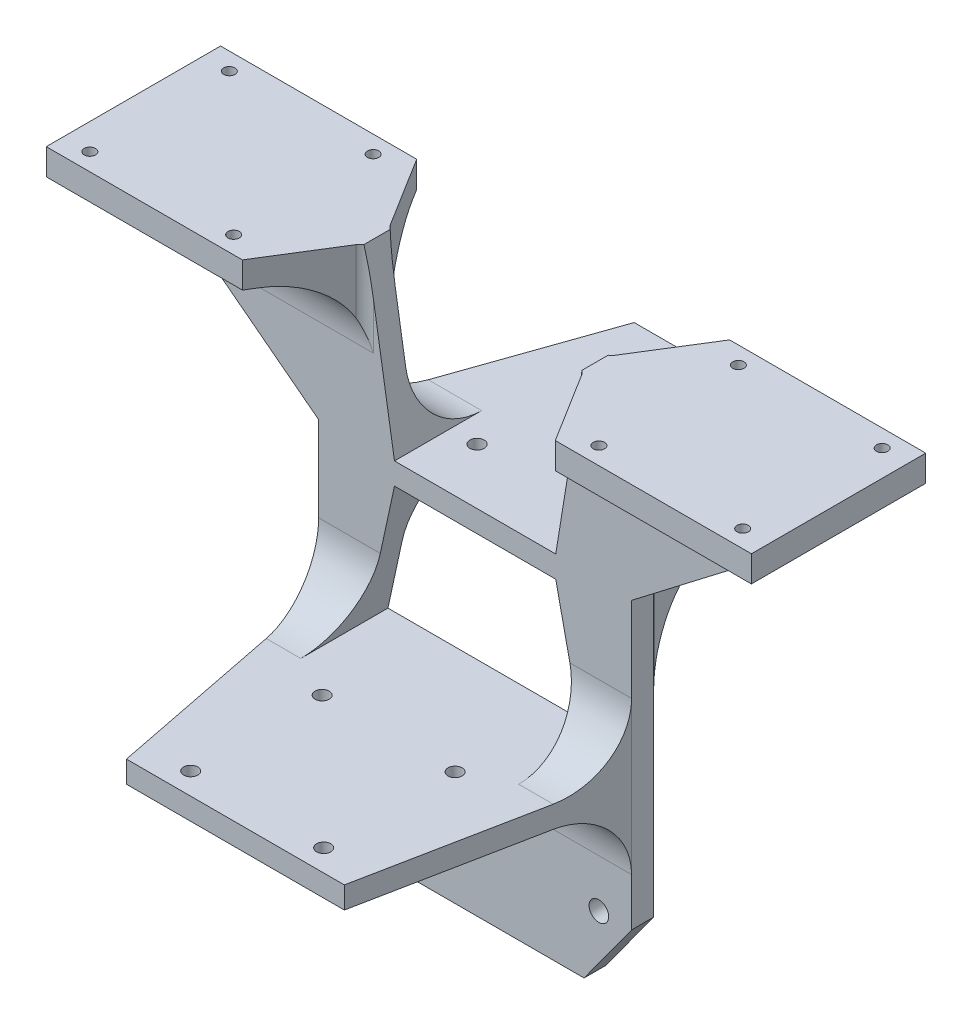
SolidWorks part; units mm, degrees
note: The reader was unsure of these and kept them because the rebuilt part matched: shared geometry of "Sketch1<5>", "Sketch1<7>", "Sketch1<8>".
ref_plane "Front Plane" through (0, 0, 0) normal (0, 0, 1) x (1, 0, 0)
ref_plane "Top Plane" through (0, 0, 0) normal (0, 1, 0) x (1, 0, 0)
ref_plane "Right Plane" through (0, 0, 0) normal (1, 0, 0) x (0, 0, -1)
sketch "Sketch1" plane through (0, 0, 0) normal (0, 0, 1) x (1, 0, 0)
  line L0 (-28.4, 0) -> (28.4, 0) construction
  line L1 (0, 0) -> (0, -15) construction
  line L2 (-25, -15) -> (25, -15)
  line L3 (-35.9, 0) -> (-25, -15)
  line L4 (25, -15) -> (35.9, 0)
  line L5 (-35.9, 0) -> (-28.4, 0) construction
  line L6 (28.4, 0) -> (35.9, 0) construction
  line L7 (-35.9, 0) -> (-35.9, 100)
  line L8 (-35.9, 100) -> (-80.9, 100)
  line L9 (-80.9, 100) -> (-80.9, 106)
  line L11 (80.9, 100) -> (80.9, 106)
  line L12 (35.9, 100) -> (80.9, 100)
  line L13 (35.9, 0) -> (35.9, 100)
  line L14 (-25, -15) -> (-25, 106) construction
  line L15 (-25, 31) -> (25, 31)
  line L16 (-25, 31) -> (-25, 26)
  line L17 (-25, 26) -> (25, 26)
  line L18 (25, 31) -> (25, 26)
  line L19 (25, -15) -> (25, 106) construction
  line L20 (-18.5, 0) -> (18.5, 0) construction
  line L21 (-18.5, 0) -> (-18.5, 106) construction
  line L22 (18.5, 0) -> (18.5, 106) construction
  line L23 (-18.5, 66) -> (-25, 106)
  line L24 (-18.5, 61) -> (18.5, 61)
  line L25 (-18.5, 61) -> (-18.5, 66)
  line L26 (-18.5, 66) -> (18.5, 66)
  line L27 (18.5, 61) -> (18.5, 66)
  line L28 (-25, 106) -> (25, 106) construction
  line L29 (25, 106) -> (18.5, 66)
  line L30 (-80.9, 106) -> (-25, 106)
  line L31 (25, 106) -> (80.9, 106)
  line L32 (-35.9, 100) -> (-35.9, 106)
  line L33 (35.9, 100) -> (35.9, 106)
  line L34 (-25, 31) -> (-18.5, 61)
  line L35 (18.5, 61) -> (25, 31)
  circle A0 centre (-28.4, 0) radius 2.25
  circle A1 centre (28.4, 0) radius 2.25
  point P4 (0, 0)
  point P12 (0, -15)
  point P19 (0, 106)
  point P30 (0, 0)
  dimension "D2" = 4.5
  dimension "D1" = 56.8
  dimension "D3" = 15
  dimension "D4" = 50
  dimension "D5" = 7.5
  dimension "D6" = 100
  dimension "D7" = 45
  dimension "D8" = 6
  dimension "D9" = 5
  dimension "D10" = 40
  dimension "D11" = 37
  dimension "D12" = 5
  dimension "D13" = 30
extrude "GPS Platforms" add sketch "Sketch1" along normal blind 22.5 and the other way blind 17.5 contours L8 L32 L30 L9 | L33 L12 L11 L31
extrude "RFD Platform" add sketch "Sketch1<5>" against normal blind 50 separate body contours L24 L27 L26 L25
sketch "Sketch1<5>" plane through (0, 0, 0) normal (0, 0, 1) x (1, 0, 0) same geometry as "Sketch1"
extrude "Structure " add sketch "Sketch1<7>" along normal blind 5 contours L13 L33 L31 L29 L27 L24 L25 L23 L30 L32 L7 L3 L2 L4 A1 A0 L15 L18 L17 L16 | L24 L27 L26 L25 | L18 L15 L16 L17 | L8 L32 L30 L9 | L33 L12 L11 L31
sketch "Sketch1<7>" plane through (0, 0, 0) normal (0, 0, 1) x (1, 0, 0) same geometry as "Sketch1"
extrude "Pix Platform" add sketch "Sketch1<8>" along normal blind 60 contours L15 L18 L17 L16
sketch "Sketch1<8>" plane through (0, 0, 0) normal (0, 0, 1) x (1, 0, 0) same geometry as "Sketch1"
sketch "Sketch2" plane through (0, 106, 0) normal (0, 1, 0) x (1, 0, 0)
  line L0 (35.9, 17.5) -> (25, 0)
  line L1 (25, 0) -> (18.5, 0) construction
  line L2 (25, -5) -> (25, 0) construction
  line L3 (25, 0) -> (35.9, 0)
  line L4 (35.9, 0) -> (35.9, 17.5)
  line L5 (35.9, -5) -> (35.9, -22.5)
  line L6 (35.9, -22.5) -> (25, -5)
  line L7 (25, -5) -> (35.9, -5)
  line L8 (0, 0) -> (0, 39.4642) construction
  line L9 (-35.9, -22.5) -> (-25, -5)
  line L10 (-35.9, -5) -> (-35.9, -22.5)
  line L11 (-25, -5) -> (-35.9, -5)
  line L12 (-25, 0) -> (-35.9, 0)
  line L13 (-35.9, 17.5) -> (-25, 0)
  line L14 (-35.9, 0) -> (-35.9, 17.5)
extrude "Support 1" add sketch "Sketch2" against normal up to surface (6 mm away) up to face at (-50.9, 100, 2.5)
sketch "Sketch3" plane through (0, 66, 0) normal (0, 1, 0) x (1, 0, 0)
  line L0 (-18.5, 50) -> (-18.5, 0)
  line L1 (-18.5, 0) -> (-36.0187, 0)
  line L2 (-36.0187, 0) -> (-18.5, 50)
  line L3 (0, 0) -> (0, 45.5249) construction
  line L4 (18.5, 0) -> (36.0187, 0)
  line L5 (18.5, 50) -> (18.5, 0)
  line L6 (36.0187, 0) -> (18.5, 50)
extrude "Support 2" add sketch "Sketch3" against normal up to surface (5 mm away) up to face at (0, 61, -15)
sketch "Sketch4" plane through (0, 31, 0) normal (0, 1, 0) x (1, 0, 0)
  line L0 (-25, -60) -> (-25, -5)
  line L1 (-25, -5) -> (-35.9, -5)
  line L2 (-35.9, -5) -> (-25, -60)
  line L3 (0, 0) -> (0, -66.3641) construction
  line L4 (25, -5) -> (35.9, -5)
  line L5 (25, -60) -> (25, -5)
  line L6 (35.9, -5) -> (25, -60)
extrude "Support 3" add sketch "Sketch4" against normal up to surface (5 mm away) up to face at (0, 26, 32.5)
sketch "Sketch5" plane through (0, 106, 0) normal (0, 1, 0) x (1, 0, 0)
  line L0 (0, 0) -> (0, 41.3908) construction
  line L7 (-74.9, -18.5) -> (-74.9, 13.5) construction
  line L8 (-74.9, -18.5) -> (-41.9, -18.5) construction
  line L9 (-41.9, -18.5) -> (-41.9, 13.5) construction
  line L10 (-74.9, 13.5) -> (-41.9, 13.5) construction
  line L11 (-74.9, -18.5) -> (-41.9, 13.5) construction
  line L12 (-41.9, -18.5) -> (-74.9, 13.5) construction
  line L13 (-80.9, -2.5) -> (-35.9, -2.5) construction
  line L14 (-80.9, 17.5) -> (-80.9, -22.5) construction
  line L15 (-35.9, 17.5) -> (-35.9, -22.5) construction
  circle A0 centre (-74.9, -18.5) radius 1.3
  circle A1 centre (-74.9, 13.5) radius 1.3
  circle A2 centre (-41.9, 13.5) radius 1.3
  circle A3 centre (-41.9, -18.5) radius 1.3
  circle A4 centre (74.9, 13.5) radius 1.3
  circle A5 centre (41.9, 13.5) radius 1.3
  circle A6 centre (41.9, -18.5) radius 1.3
  circle A7 centre (74.9, -18.5) radius 1.3
  point P1 (-58.4, -2.5)
  point P2 (-58.4, -2.5)
  point P7 (-58.4, -2.5)
  dimension "D3" = 2.6
  dimension "D1" = 32
  dimension "D2" = 33
extrude "GPS Mounting holes" cut sketch "Sketch5" against normal up to next
sketch "Sketch6" plane through (0, 0, 5) normal (0, 0, 1) x (1, 0, 0)
  line L0 (80.9, 100) -> (35.9, 65.5)
  line L1 (35.9, 31) -> (35.9, 100) construction
  line L2 (35.9, 65.5) -> (35.9, 100)
  line L3 (35.9, 100) -> (80.9, 100)
  line L4 (0, 0) -> (0, 110.011) construction
  line L5 (-35.9, 65.5) -> (-35.9, 100)
  line L6 (-80.9, 100) -> (-35.9, 65.5)
  line L7 (-35.9, 100) -> (-80.9, 100)
extrude "Support 4" add sketch "Sketch6" against normal up to surface (5 mm away) up to face at (28.06, 87.6, 0)
sketch "Sketch7" plane through (0, 66, 0) normal (0, 1, 0) x (1, 0, 0)
  line L0 (-12.35, 7.8) -> (0, 7.8) construction
  line L1 (0, 7.8) -> (0, 45) construction
  line L2 (0, -5) -> (0, 50) construction
  line L3 (-18.5, -5) -> (18.5, -5) construction
  line L4 (-18.5, 50) -> (18.5, 50) construction
  circle A0 centre (0, 45) radius 1.65
  circle A1 centre (-12.35, 7.8) radius 1.65
  circle A2 centre (12.35, 7.8) radius 1.65
  dimension "D1" = 3.3
  dimension "D2" = 37.2
  dimension "D3" = 12.35
  dimension "D4" = 5
extrude "RFD Mounting holes" cut sketch "Sketch7" against normal up to next
sketch "Sketch8" plane through (0, 31, 0) normal (0, 1, 0) x (1, 0, 0)
  line L0 (0, -60) -> (0, -37.1982) construction
  line L1 (0, -37.1982) -> (0, -47.3498) construction
  line L2 (15.25, -55) -> (15.25, -24.85) construction
  line L3 (15.25, -55) -> (-15.25, -55) construction
  line L4 (15.25, -24.85) -> (-15.25, -24.85) construction
  line L5 (-15.25, -55) -> (-15.25, -24.85) construction
  line L6 (15.25, -55) -> (-15.25, -24.85) construction
  line L7 (15.25, -24.85) -> (-15.25, -55) construction
  line L8 (-25, -60) -> (25, -60) construction
  circle A0 centre (-15.25, -55) radius 1.625
  circle A1 centre (-15.25, -24.85) radius 1.625
  circle A2 centre (15.25, -24.85) radius 1.625
  circle A3 centre (15.25, -55) radius 1.625
  point P4 (0, -39.925)
  point P12 (0, 0)
  point P13 (0, -60)
  dimension "D3" = 3.25
  dimension "D1" = 30.5
  dimension "D2" = 30.15
  dimension "D4" = 5
extrude "Cut-Extrude3" cut sketch "Sketch8" against normal up to next
fillet "Fillet2" radius 15 1 edges at (0, 26, 5)
fillet "Fillet3" radius 15 2 edges at (30.45, 31, 5) (-30.45, 31, 5)
fillet "Fillet4" radius 15 3 edges at (27.2593, 66, 0) (27.2, 61, 0) (-27.2, 61, 0)
fillet "Fillet5" radius 15 4 edges at (52.95, 100, 0) (52.95, 100, 5) (-52.95, 100, 5) (-52.95, 100, 0)
fillet "Fillet6" radius 3 6 edges at (25, 95.5, 0) (25, 95.5, 5) (-25, 95.5, 5) (-25, 95.5, 0) (27.7365, 95.6066, 9.3934) (-27.7365, 95.6066, -4.3934)
